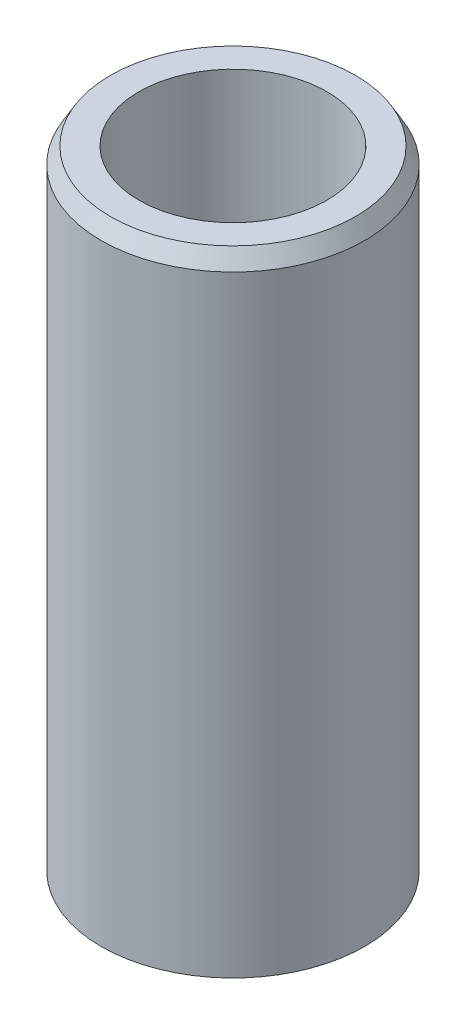
SolidWorks part; units mm, degrees
ref_plane "Front Plane" through (0, 0, 0) normal (0, 0, 1) x (1, 0, 0)
ref_plane "Top Plane" through (0, 0, 0) normal (0, 1, 0) x (1, 0, 0)
ref_plane "Right Plane" through (0, 0, 0) normal (1, 0, 0) x (0, 0, -1)
sketch "Sketch1" plane through (0, 0, 0) normal (0, 1, 0) x (1, 0, 0)
  circle A0 centre (0, 0) radius 15
  dimension "SHAFT_OD" = 30
extrude "Boss-Extrude1" add sketch "Sketch1" along normal blind 72.5232
sketch "Sketch2" plane through (0, 0, 0) normal (0, 1, 0) x (1, 0, 0)
  circle A0 centre (0, 0) radius 10.7094
  dimension "BORE_D" = 21.4188
extrude "Cut-Extrude1" cut sketch "Sketch2" along normal through all
chamfer "Chamfer1" distance 1.834 angle 30 2 edges at (0, 72.5232, 15) (0, 0, 15) first distance on face at (0, 72.5232, 15) first distance on face at (0, 0, 10.7094)
